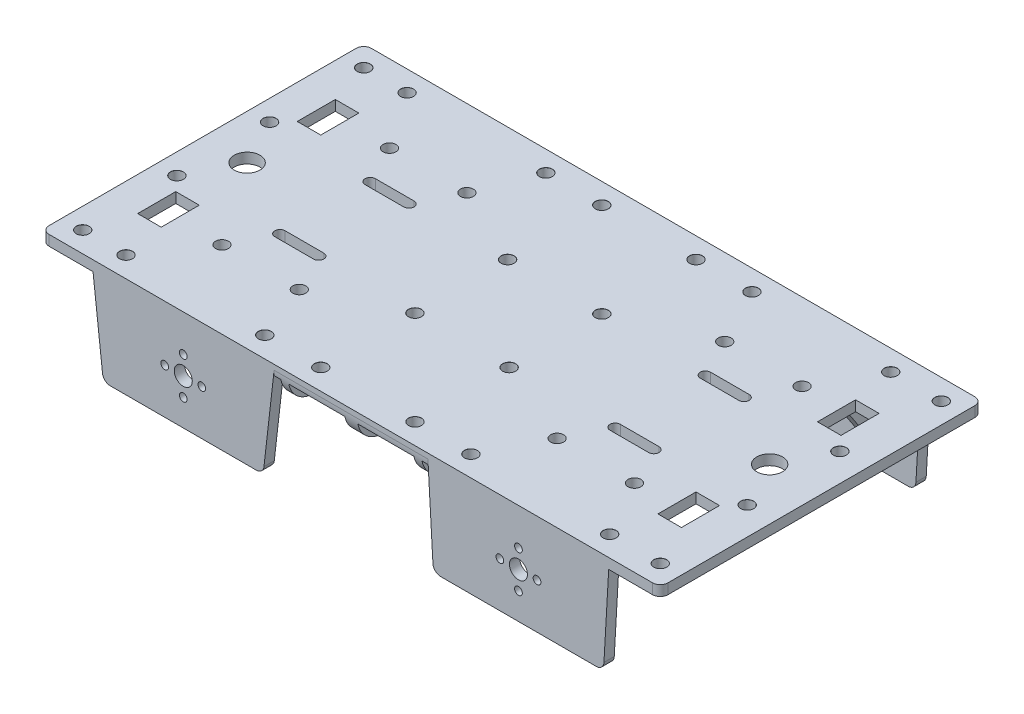
SolidWorks part; units mm, degrees
ref_plane "前视基准面" through (0, 0, 0) normal (0, 0, 1) x (1, 0, 0)
ref_plane "上视基准面" through (0, 0, 0) normal (0, 1, 0) x (1, 0, 0)
ref_plane "右视基准面" through (0, 0, 0) normal (1, 0, 0) x (0, 0, -1)
other "Configuration Table"
sketch "草图2" plane through (0, 0, 0) normal (0, 1, 0) x (1, 0, 0)
  line L1 (-120, -62.5) -> (120, -62.5)
  line L2 (-120, -62.5) -> (-120, 62.5)
  line L3 (-120, 62.5) -> (120, 62.5)
  line L4 (120, -62.5) -> (120, 62.5)
  line L5 (-120, -62.5) -> (120, 62.5) construction
  line L6 (-120, 62.5) -> (120, -62.5) construction
  point P0 (0, 0)
  dimension "D1" = 125
  dimension "D2" = 240
extrude "凸台-拉伸1" add sketch "草图2" along normal blind 4 and the other way blind 0.001
fillet "圆角1" radius 3 4 edges at (120, 1.9995, 62.5) (120, 1.9995, -62.5) (-120, 1.9995, -62.5) (-120, 1.9995, 62.5)
sketch "草图4" plane through (0, -0.001, 0) normal (0, -1, 0) x (1, 0, 0)
  line L0 (0, 62.5) -> (0, -62.5) construction
  line L1 (-117, 62.5) -> (117, 62.5) construction
  line L2 (117, -62.5) -> (-117, -62.5) construction
  line L3 (30, 62.5) -> (30, 58.5)
  line L4 (30, 58.5) -> (100, 58.5)
  line L5 (100, 58.5) -> (100, 62.5)
  line L6 (100, 62.5) -> (30, 62.5)
  line L7 (-100, 58.5) -> (-100, 62.5)
  line L8 (-30, 58.5) -> (-100, 58.5)
  line L9 (-30, 62.5) -> (-30, 58.5)
  line L10 (-100, 62.5) -> (-30, 62.5)
  line L11 (-120, 0) -> (120, 0) construction
  line L12 (-120, -59.5) -> (-120, 59.5) construction
  line L13 (120, 59.5) -> (120, -59.5) construction
  line L14 (100, -58.5) -> (100, -62.5)
  line L15 (30, -58.5) -> (100, -58.5)
  line L16 (30, -62.5) -> (30, -58.5)
  line L17 (100, -62.5) -> (30, -62.5)
  line L18 (-30, -58.5) -> (-100, -58.5)
  line L19 (-30, -62.5) -> (-30, -58.5)
  line L20 (-100, -62.5) -> (-30, -62.5)
  line L21 (-100, -58.5) -> (-100, -62.5)
  point P28 (30, 60.5)
  dimension "D1" = 4
  dimension "D2" = 70
  dimension "D3" = 30
extrude "凸台-拉伸3" add sketch "草图4" along normal blind 35
sketch "草图7" plane through (0, 0, 62.5) normal (0, 0, 1) x (1, 0, 0)
  line L0 (-100, -0.001) -> (-96, -35.001)
  line L1 (-30, -35.001) -> (-100, -35.001) construction
  line L2 (-65, -35.001) -> (-65, 4) construction
  line L3 (-117, 4) -> (117, 4) construction
  line L4 (-30, -0.001) -> (-34, -35.001)
  line L5 (-100, -35.001) -> (-100, -0.001) construction
  line L6 (-96, -35.001) -> (-100, -35.001)
  line L7 (-100, -35.001) -> (-100, -0.001)
  line L8 (-30, -0.001) -> (-30, -35.001)
  line L9 (-30, -35.001) -> (-34, -35.001)
  dimension "D1" = 4
extrude "切除-拉伸1" cut sketch "草图7" against normal through all both and the other way through all
sketch "草图9" plane through (0, 0, 62.5) normal (0, 0, 1) x (1, 0, 0)
  line L0 (30, -0.001) -> (32, -35.001)
  line L1 (32, -35.001) -> (30, -35.001)
  line L2 (30, -35.001) -> (30, -0.001) construction
  line L3 (100, -35.001) -> (30, -35.001) construction
  line L4 (30, -35.001) -> (30, -0.001)
  line L5 (65, -35.001) -> (65, 4) construction
  line L6 (-117, 4) -> (117, 4) construction
  line L7 (98, -35.001) -> (100, -35.001)
  line L8 (100, -0.001) -> (98, -35.001)
  line L9 (100, -35.001) -> (100, -0.001)
  dimension "D1" = 2
extrude "切除-拉伸2" cut sketch "草图9" against normal through all both and the other way through all
fillet "圆角2" radius 3 1 edges at (-96, -35.001, 60.5)
fillet "圆角3" radius 3 7 edges at (98, -35.001, -60.5) (32, -35.001, -60.5) (98, -35.001, 60.5) (32, -35.001, 60.5) (-34, -35.001, -60.5) (-96, -35.001, -60.5) (-34, -35.001, 60.5)
sketch "草图11" plane through (0, 4, 0) normal (0, 1, 0) x (1, 0, 0)
  line L0 (0, -62.5) -> (0, 62.5) construction
  line L1 (-117, -62.5) -> (117, -62.5) construction
  line L2 (117, 62.5) -> (-117, 62.5) construction
  line L3 (-65, -62.5) -> (-65, 62.5) construction
  line L5 (-120, 0) -> (120, 0) construction
  line L6 (-120, 59.5) -> (-120, -59.5) construction
  line L7 (120, -59.5) -> (120, 59.5) construction
  line L8 (-72.5, -17.5) -> (-57.5, -17.5) construction
  line L9 (-72.5, -15.5) -> (-57.5, -15.5)
  line L10 (-72.5, -19.5) -> (-57.5, -19.5)
  line L11 (-72.5, 17.5) -> (-57.5, 17.5) construction
  line L12 (-72.5, 15.5) -> (-57.5, 15.5)
  line L13 (-72.5, 19.5) -> (-57.5, 19.5)
  line L14 (72.5, -17.5) -> (57.5, -17.5) construction
  line L15 (72.5, -15.5) -> (57.5, -15.5)
  line L16 (72.5, -19.5) -> (57.5, -19.5)
  line L17 (72.5, 17.5) -> (57.5, 17.5) construction
  line L18 (72.5, 15.5) -> (57.5, 15.5)
  line L19 (72.5, 19.5) -> (57.5, 19.5)
  arc A0 (-72.5, -15.5) -> (-72.5, -19.5) centre (-72.5, -17.5) ccw
  arc A1 (-57.5, -19.5) -> (-57.5, -15.5) centre (-57.5, -17.5) ccw
  circle A2 centre (-80, -32.5) radius 2.5
  circle A3 centre (-50, -32.5) radius 2.5
  circle A4 centre (-50, 32.5) radius 2.5
  arc A5 (-72.5, 15.5) -> (-72.5, 19.5) centre (-72.5, 17.5) cw
  arc A6 (-57.5, 19.5) -> (-57.5, 15.5) centre (-57.5, 17.5) cw
  circle A7 centre (-80, 32.5) radius 2.5
  circle A8 centre (50, -32.5) radius 2.5
  circle A9 centre (50, 32.5) radius 2.5
  circle A10 centre (80, -32.5) radius 2.5
  arc A11 (72.5, -15.5) -> (72.5, -19.5) centre (72.5, -17.5) cw
  arc A12 (57.5, -19.5) -> (57.5, -15.5) centre (57.5, -17.5) cw
  arc A13 (72.5, 15.5) -> (72.5, 19.5) centre (72.5, 17.5) ccw
  arc A14 (57.5, 19.5) -> (57.5, 15.5) centre (57.5, 17.5) ccw
  circle A15 centre (80, 32.5) radius 2.5
  point P16 (-65, -17.5)
  point P29 (-65, 17.5)
  point P44 (65, -17.5)
  point P51 (65, 17.5)
  dimension "D6" = 5
  dimension "D1" = 65
  dimension "D2" = 45
  dimension "D3" = 4
  dimension "D4" = 15
  dimension "D5" = 15
  dimension "D7" = 15
extrude "切除-拉伸4" cut sketch "草图11" against normal up to next and the other way through all
sketch "草图18" plane through (0, 4, 0) normal (0, 1, 0) x (1, 0, 0)
  line L0 (-120, 0) -> (120, 0) construction
  line L1 (-120, 59.5) -> (-120, -59.5) construction
  line L2 (120, -59.5) -> (120, 59.5) construction
  line L3 (0, -62.5) -> (0, 62.5) construction
  line L4 (-117, -62.5) -> (117, -62.5) construction
  line L5 (117, 62.5) -> (-117, 62.5) construction
  point P0 (-112, 54.5)
  point P14 (-112, -54.5)
  point P16 (112, -54.5)
  point P17 (112, 54.5)
  dimension "D1" = 8
  dimension "D2" = 8
hole_wizard "Ø5.0 (5) 直径孔4" positions "草图18" profile "草图21" hole size "Ø5.0" standard "GB" end condition through all
sketch "草图21" plane through (-112, 4, -54.5) normal (1, 0, 0) x (0, 0, 1)
  line L0 (0, 0) -> (0, 39.001)
  line L1 (0, 39.001) -> (2.5, 39.001)
  line L2 (2.5, 39.001) -> (2.5, 0.025)
  line L3 (2.5, 0.025) -> (2.525, 0)
  line L5 (2.525, 0) -> (0, 0)
  line L6 (-2.5, 0.025) -> (-2.525, 0) construction
  line L11 (0, -6.35) -> (0, 107.95) construction
  dimension "通孔孔直径" = 5
  dimension "通孔孔深度" = 39.001
  dimension "近端锥形沉头孔直径" = 5.05
  dimension "近端锥形沉头孔角度" = 90
sketch "草图22" plane through (0, 4, 0) normal (0, 1, 0) x (1, 0, 0)
  line L0 (-120, 0) -> (120, 0) construction
  line L1 (-120, 59.5) -> (-120, -59.5) construction
  line L2 (120, -59.5) -> (120, 59.5) construction
  line L3 (-1.4058, -62.5) -> (-1.4058, 62.5) construction
  line L4 (-117, -62.5) -> (117, -62.5) construction
  line L5 (117, 62.5) -> (-117, 62.5) construction
  circle A0 centre (-102.7384, 0) radius 5
  circle A1 centre (99.9268, 0) radius 5
  point P12 (-95.1921, 54.5)
  point P13 (-41.3704, 54.5)
  point P14 (-19.6811, 54.5)
  point P15 (-112, 17.9739)
  point P16 (-19.6811, 17.9739)
  point P17 (-19.6811, -17.9739)
  point P18 (-19.6811, -54.5)
  point P19 (-41.3704, -54.5)
  point P20 (-95.1921, -54.5)
  point P21 (-112, -17.9739)
  point P22 (16.8695, -54.5)
  point P23 (38.5588, -54.5)
  point P24 (92.3805, -54.5)
  point P25 (109.1884, -17.9739)
  point P26 (16.8695, -17.9739)
  point P27 (16.8695, 17.9739)
  point P28 (109.1884, 17.9739)
  point P29 (16.8695, 54.5)
  point P30 (38.5588, 54.5)
  point P31 (92.3805, 54.5)
  dimension "D5" = 10
  dimension "D1" = 8
  dimension "D2" = 8
  dimension "D3" = 8
  dimension "D4" = 8
hole_wizard "Ø5.0 (5) 直径孔5" positions "草图23" profile "草图24" hole size "Ø5.0" standard "GB" end condition through all
sketch "草图23" plane through (0, 4, 0) normal (0, 1, 0) x (1, 0, 0)
  point P0 (-95.1921, 54.5)
  point P3 (-41.3704, 54.5)
  point P6 (-19.6811, 54.5)
  point P9 (-19.6811, 17.9739)
  point P12 (-112, 17.9739)
  point P15 (-112, -17.9739)
  point P18 (-95.1921, -54.5)
  point P21 (-41.3704, -54.5)
  point P24 (-19.6811, -54.5)
  point P27 (-19.6811, -17.9739)
  point P30 (16.8695, 17.9739)
  point P33 (16.8695, -17.9739)
  point P36 (16.8695, 54.5)
  point P39 (38.5588, 54.5)
  point P42 (92.3805, 54.5)
  point P45 (109.1884, 17.9739)
  point P48 (109.1884, -17.9739)
  point P53 (92.3805, -54.5)
  point P56 (38.5588, -54.5)
  point P59 (16.8695, -54.5)
sketch "草图24" plane through (-95.1921, 4, -54.5) normal (1, 0, 0) x (0, 0, 1)
  line L0 (0, 0) -> (0, 39.001)
  line L1 (0, 39.001) -> (2.5, 39.001)
  line L2 (2.5, 39.001) -> (2.5, 0.025)
  line L3 (2.5, 0.025) -> (2.525, 0)
  line L5 (2.525, 0) -> (0, 0)
  line L6 (-2.5, 0.025) -> (-2.525, 0) construction
  line L11 (0, -6.35) -> (0, 107.95) construction
  dimension "通孔孔直径" = 5
  dimension "通孔孔深度" = 39.001
  dimension "近端锥形沉头孔直径" = 5.05
  dimension "近端锥形沉头孔角度" = 90
sketch "草图25" plane through (0, 0, 62.5) normal (0, 0, 1) x (1, 0, 0)
  line L0 (-65, -35.001) -> (-65, 4) construction
  line L1 (-36.6767, -35.001) -> (-93.3233, -35.001) construction
  line L2 (-120, 4) -> (120, 4) construction
  line L3 (0, 0) -> (0, 4)
sketch "草图26" plane through (0, 4, 0) normal (0, 1, 0) x (1, 0, 0)
  line L0 (-120, 0) -> (120, 0) construction
  line L1 (-106.8552, 38.3295) -> (-97.7252, 38.3295)
  line L2 (-106.8552, 38.3295) -> (-106.8552, 23.5533)
  line L3 (-106.8552, 23.5533) -> (-97.7252, 23.5533)
  line L4 (-97.7252, 38.3295) -> (-97.7252, 23.5533)
  line L5 (-1.4058, 62.5) -> (-1.4058, -62.5) construction
  line L6 (-106.8552, -23.5533) -> (-97.7252, -23.5533)
  line L7 (-97.7252, -38.3295) -> (-97.7252, -23.5533)
  line L8 (-106.8552, -38.3295) -> (-97.7252, -38.3295)
  line L9 (-106.8552, -38.3295) -> (-106.8552, -23.5533)
  line L10 (104.0436, -38.3295) -> (104.0436, -23.5533)
  line L11 (104.0436, -38.3295) -> (94.9136, -38.3295)
  line L12 (94.9136, -38.3295) -> (94.9136, -23.5533)
  line L13 (104.0436, -23.5533) -> (94.9136, -23.5533)
  line L14 (104.0436, 23.5533) -> (94.9136, 23.5533)
  line L15 (94.9136, 38.3295) -> (94.9136, 23.5533)
  line L16 (104.0436, 38.3295) -> (94.9136, 38.3295)
  line L17 (104.0436, 38.3295) -> (104.0436, 23.5533)
extrude "切除-拉伸5" cut sketch "草图26" against normal blind 10
extrude "切除-拉伸6" cut sketch "草图22" against normal blind 10
sketch "草图28" plane through (0, 0, 62.5) normal (0, 0, 1) x (1, 0, 0)
sketch "草图29" plane through (0, 0, 62.5) normal (0, 0, 1) x (1, 0, 0)
  line L0 (-65, 4) -> (-65, -35.001) construction
  line L1 (0, 4) -> (0, 0) construction
  line L2 (65, -35.001) -> (65, 4) construction
  line L3 (95.1665, -35.001) -> (34.8335, -35.001) construction
  line L4 (-117, 4) -> (117, 4) construction
  line L5 (-36.6767, -35.001) -> (-93.3233, -35.001) construction
  circle A0 centre (-65, -17.501) radius 3.5
  circle A1 centre (-65, -10.301) radius 1.5
  circle A2 centre (-57.8, -17.501) radius 1.5
  circle A3 centre (-65, -24.701) radius 1.5
  circle A4 centre (-72.2, -17.501) radius 1.5
  circle A5 centre (57.8, -17.501) radius 1.5
  circle A6 centre (72.2, -17.501) radius 1.5
  circle A7 centre (65, -24.701) radius 1.5
  circle A8 centre (65, -17.501) radius 3.5
  circle A9 centre (65, -10.301) radius 1.5
  dimension "D1" = 7
  dimension "D3" = 3
  dimension "D2" = 17.5
  dimension "D4" = 7.2
  dimension "D5" = 4
extrude "切除-拉伸7" cut sketch "草图29" against normal through all
sketch "草图30" plane through (0, -0.001, 0) normal (0, -1, 0) x (1, 0, 0)
  line L0 (83.6451, -58.5) -> (83.6451, -38.6442)
  line L1 (95.1665, -58.5) -> (34.8335, -58.5) construction
  line L2 (83.6451, -38.6442) -> (87.2488, -38.6442)
  line L3 (87.2488, -38.6442) -> (87.2488, -58.5)
  line L4 (100, -58.5) -> (30, -58.5) construction
  line L5 (83.6451, -58.5) -> (87.2488, -58.5)
extrude "凸台-拉伸4" add sketch "草图30" along normal blind 30
sketch "草图31" plane through (87.2488, 0, 0) normal (1, 0, 0) x (0, 0, -1)
  line L0 (38.6442, -0.001) -> (58.5, -30.001)
  line L1 (58.5, -30.001) -> (38.6442, -30.001)
  line L2 (38.6442, -30.001) -> (38.6442, -0.001)
extrude "切除-拉伸8" cut sketch "草图31" against normal up to next
sketch "草图32" plane through (0, -0.001, 0) normal (0, -1, 0) x (1, 0, 0)
  line L0 (65, 58.5) -> (65, -58.5) construction
  line L1 (34.8335, 58.5) -> (95.1665, 58.5) construction
  line L2 (95.1665, -58.5) -> (34.8335, -58.5) construction
ref_plane "基准面1" through (65, 0, 0) normal (-1, 0, 0) x (0, 0, -1)
mirror "镜向1" about plane through (65, 0, 0) normal (-1, 0, 0) of "切除-拉伸8"
mirror "镜向2" about plane through (65, 0, 0) normal (-1, 0, 0) of "凸台-拉伸4"
mirror "镜向4" about plane through (65, 0, 0) normal (-1, 0, 0) of "切除-拉伸8"
mirror "镜向6" about plane through (0, 0, 0) normal (1, 0, 0) of "镜向4", "凸台-拉伸4", "镜向2", "切除-拉伸8"
mirror "镜向7" about plane through (0, 0, 0) normal (0, 0, 1) of "镜向6", "凸台-拉伸4", "切除-拉伸8", "镜向2", "镜向4"
sketch "草图33" plane through (0, -0.001, 0) normal (0, -1, 0) x (1, 0, 0)
  line L0 (0, 62.5) -> (0, -62.5) construction
  line L1 (-30, 62.5) -> (30, 62.5) construction
  line L2 (30, -62.5) -> (-30, -62.5) construction
  line L3 (2.5237, 62.5) -> (-2.5237, 62.5)
  line L4 (-2.5237, 62.5) -> (-2.5237, -62.5)
  line L5 (-2.5237, -62.5) -> (2.5237, -62.5)
  line L6 (-27.372, 62.5) -> (-27.372, -62.5)
  line L7 (-27.372, -62.5) -> (-24.266, -62.5)
  line L8 (-24.266, -62.5) -> (-24.266, 62.5)
  line L9 (-24.266, 62.5) -> (-27.372, 62.5)
  line L10 (2.5237, 62.5) -> (2.5237, -62.5)
  line L11 (24.266, -62.5) -> (24.266, 62.5)
  line L12 (27.372, -62.5) -> (24.266, -62.5)
  line L13 (27.372, 62.5) -> (27.372, -62.5)
  line L14 (24.266, 62.5) -> (27.372, 62.5)
extrude "凸台-拉伸5" add sketch "草图33" along normal blind 8
fillet "圆角4" radius 10 2 edges at (0, -8.001, 62.5) (-25.819, -8.001, -62.5)
